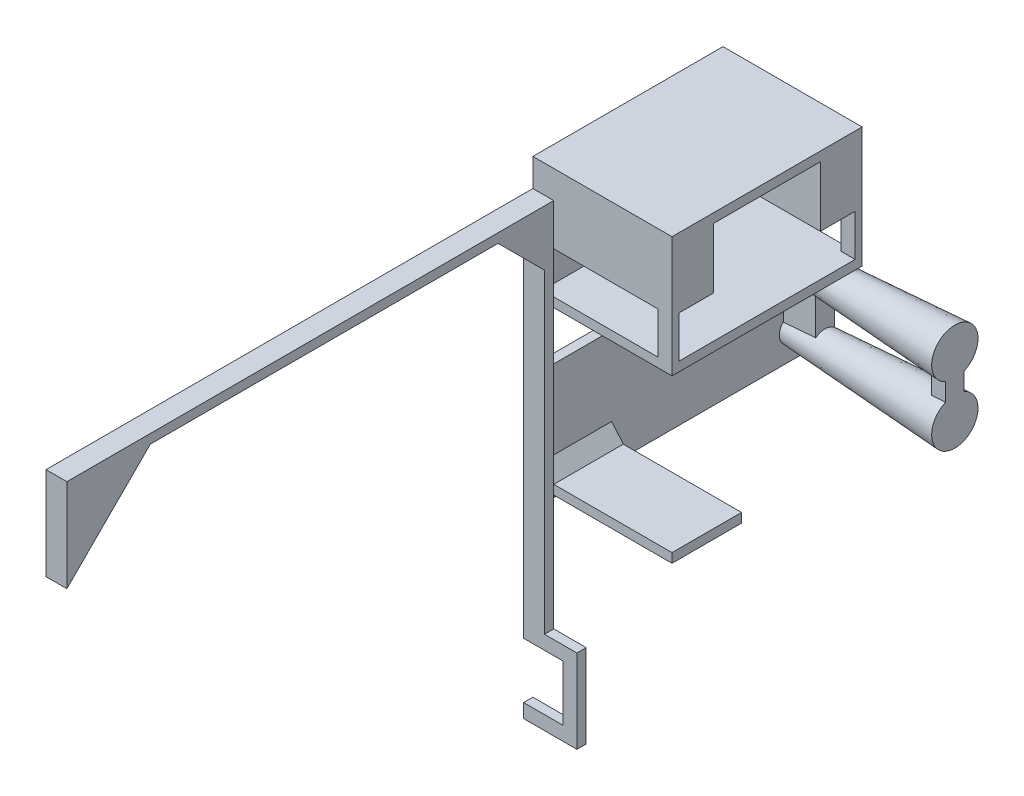
SolidWorks part; units mm, degrees
ref_plane "Front Plane" through (0, 0, 0) normal (0, 0, 1) x (1, 0, 0)
ref_plane "Top Plane" through (0, 0, 0) normal (0, 1, 0) x (1, 0, 0)
ref_plane "Right Plane" through (0, 0, 0) normal (1, 0, 0) x (0, 0, -1)
sketch "Sketch6" plane through (0, 0, 0) normal (1, 0, 0) x (0, 0, -1)
  line L1 (0, 0) -> (105, 0)
  line L2 (0, 0) -> (0, -83)
  line L3 (0, -83) -> (105, -83)
  line L4 (105, 0) -> (105, -83)
  dimension "D1" = 105
  dimension "D2" = 83
extrude "Boss-Extrude3" add sketch "Sketch6" along normal blind 4.5
sketch "Sketch9" plane through (0, -83, 0) normal (0, -1, 0) x (1, 0, 0)
  line L0 (4.5, 0) -> (4.5, -105) construction
  line L1 (0, 0) -> (0, -105) construction
  line L2 (4.5, -2) -> (1.5, -2)
  line L3 (4.5, -2) -> (4.5, -103)
  line L4 (4.5, -103) -> (1.5, -103)
  line L5 (1.5, -2) -> (1.5, -103)
  line L6 (4.5, 0) -> (0, 0) construction
  line L7 (4.5, -105) -> (0, -105) construction
  dimension "D1" = 1.5
  dimension "D2" = 2
  dimension "D3" = 2
extrude "Cut-Extrude6" cut sketch "Sketch9" against normal blind 81
sketch "Sketch10" plane through (0, 0, -2) normal (0, 0, -1) x (-1, 0, 0)
  line L1 (-4.5, -2) -> (-3.5, -2)
  line L2 (-4.5, -2) -> (-4.5, -10)
  line L3 (-4.5, -10) -> (-3.5, -10)
  line L4 (-3.5, -2) -> (-3.5, -10)
  dimension "D1" = 1
  dimension "D2" = 8
extrude "Boss-Extrude4" add sketch "Sketch10" along normal blind 8
sketch "Sketch11" plane through (0, 0, -103) normal (0, 0, 1) x (1, 0, 0)
  line L1 (4.5, -2) -> (3.2738, -2)
  line L2 (4.5, -2) -> (4.5, -7)
  line L3 (4.5, -7) -> (3.2738, -7)
  line L4 (3.2738, -2) -> (3.2738, -7)
  dimension "D1" = 5
extrude "Boss-Extrude5" add sketch "Sketch11" along normal blind 5
sketch "Sketch18" plane through (4.5, 0, 0) normal (1, 0, 0) x (0, 0, -1)
  line L0 (103, -12) -> (93, -2)
  line L1 (103, -7) -> (103, -83) construction
  line L2 (98, -2) -> (10, -2) construction
  line L3 (103, -12) -> (103, -2)
  line L4 (103, -2) -> (93, -2)
  line L5 (18, -2) -> (2, -2)
  line L6 (2, -2) -> (2, -18)
  line L7 (2, -10) -> (2, -83) construction
  line L8 (2, -18) -> (18, -2)
  dimension "D1" = 0
  dimension "D2" = 10
  dimension "D3" = 0
  dimension "D4" = 16
  dimension "D5" = 22.6274
extrude "Boss-Extrude12" add sketch "Sketch18" against normal up to vertex (1.2262 mm away) up to point (3.2738, -7, -98)
sketch "Sketch27" plane through (0, 0, 0) normal (-1, 0, 0) x (0, 0, 1)
  line L0 (-105, -83) -> (-105, 0) construction
  line L1 (-105, -55) -> (-120, -55)
  line L2 (-105, -55) -> (-105, -53)
  line L3 (-105, -53) -> (-120, -53)
  line L4 (-120, -55) -> (-120, -53)
  line L5 (-125.5, -18) -> (-125.5, 21.7068) construction
  line L6 (-105, -20) -> (-146, -20)
  line L7 (-105, -20) -> (-105, -18)
  line L8 (-105, -18) -> (-146, -18)
  line L9 (-146, -20) -> (-146, -18)
  line L10 (-105, -9) -> (-114, -9)
  line L11 (-105, -9) -> (-105, 6)
  line L12 (-105, 6) -> (-114, 6)
  line L13 (-114, -9) -> (-114, 6)
  line L14 (-146, 6) -> (-137, 6)
  line L15 (-137, -9) -> (-137, 6)
  line L16 (-146, -9) -> (-137, -9)
  line L17 (-146, -9) -> (-146, 6)
  dimension "D1" = 15
  dimension "D2" = 28
  dimension "D3" = 63
  dimension "D4" = 41
  dimension "D5" = 2
  dimension "D6" = 2
  dimension "D7" = 9
  dimension "D8" = 15
  dimension "D9" = 9
extrude "Boss-Extrude20" add sketch "Sketch27" against normal blind 30
sketch "Sketch28" plane through (30, 0, 0) normal (1, 0, 0) x (0, 0, -1)
  line L0 (146, -9) -> (137, -9) construction
  line L1 (146, -20) -> (144.5, -20)
  line L2 (146, -20) -> (146, -9)
  line L3 (146, -9) -> (144.5, -9)
  line L4 (144.5, -20) -> (144.5, -9)
  line L5 (125.5, -18) -> (125.5, -4.7212) construction
  line L6 (105, -18) -> (146, -18) construction
  line L7 (105, -9) -> (106.5, -9)
  line L8 (106.5, -20) -> (106.5, -9)
  line L9 (105, -20) -> (106.5, -20)
  line L10 (105, -20) -> (105, -9)
  dimension "D1" = 1.5
extrude "Boss-Extrude21" add sketch "Sketch28" against normal blind 3
sketch "Sketch29" plane through (30, 0, 0) normal (1, 0, 0) x (0, 0, -1)
  line L0 (105, -20) -> (105, 6) construction
  line L1 (146, 6) -> (105, 6)
  line L2 (146, 6) -> (146, 4)
  line L3 (146, 4) -> (105, 4)
  line L4 (105, 6) -> (105, 4)
  dimension "D1" = 2
extrude "Boss-Extrude22" add sketch "Sketch29" against normal up to vertex (30 mm away) up to point (0, 6, -105)
sketch "Sketch30" plane through (0, 0, -105) normal (0, 0, -1) x (-1, 0, 0)
  line L0 (0, -83) -> (0, -55) construction
  line L1 (0, -58) -> (-2, -58)
  line L2 (0, -58) -> (0, -33)
  line L3 (0, -33) -> (-2, -33)
  line L4 (-2, -58) -> (-2, -33)
  dimension "D1" = 2
  dimension "D2" = 25
  dimension "D3" = 25
extrude "Boss-Extrude23" add sketch "Sketch30" along normal blind 60
sketch "Sketch31" plane through (2, 0, 0) normal (1, 0, 0) x (0, 0, -1)
  line L0 (165, -58) -> (105, -58) construction
  line L1 (165, -33) -> (165, -58) construction
  line L2 (165, -45.5) -> (129.1416, -45.5) construction
  circle A0 centre (159, -52) radius 5
  circle A1 centre (159, -39) radius 5
  dimension "D1" = 10
  dimension "D2" = 6
  dimension "D3" = 6
extrude "Boss-Extrude24" add sketch "Sketch31" along normal blind 35
draft "Draft1" type of draft neutral plane draft angle 3.5 faces to draft 1 face at (37, -52, -164) neutral plane through (37, -52, -159) neutral plane normal (1, 0, 0) reverse direction yes parameters "D1"=3.5
draft "Draft3" type of draft neutral plane draft angle 3.5 faces to draft 1 face at (37, -39, -154) neutral plane through (37, -39, -159) neutral plane normal (1, 0, 0) reverse direction yes parameters "D1"=3.5
sketch "Sketch32" plane through (2, 0, 0) normal (1, 0, 0) x (0, 0, -1)
  line L1 (161, -53) -> (157, -53)
  line L2 (161, -53) -> (161, -38)
  line L3 (161, -38) -> (157, -38)
  line L4 (157, -53) -> (157, -38)
  circle A0 centre (159, -52) radius 2.8593 construction
  circle A1 centre (159, -39) radius 2.8593 construction
  dimension "D1" = 2
  dimension "D2" = 2
  dimension "D3" = 1
  dimension "D4" = 1
  dimension "D5" = 2
extrude "Boss-Extrude25" add sketch "Sketch32" along normal blind 7
sketch "Sketch33" plane through (37, 0, 0) normal (1, 0, 0) x (0, 0, -1)
  line L1 (157, -39) -> (161, -39)
  line L2 (157, -39) -> (157, -52)
  line L3 (157, -52) -> (161, -52)
  line L4 (161, -39) -> (161, -52)
  circle A0 centre (159, -39) radius 5 construction
  circle A1 centre (159, -52) radius 5 construction
  point P6 (159, -39)
  dimension "D1" = 0
  dimension "D2" = 4
  dimension "D3" = 0
  dimension "D4" = 0
extrude "Boss-Extrude26" add sketch "Sketch33" against normal blind 3
sketch "Sketch34" plane through (4.5, 0, 0) normal (1, 0, 0) x (0, 0, -1)
  line L0 (105, -83) -> (105, -55) construction
  line L1 (103, -83) -> (105, -83)
  line L2 (103, -83) -> (103, -80)
  line L3 (103, -80) -> (105, -80)
  line L4 (105, -83) -> (105, -80)
  dimension "D1" = 3
extrude "Boss-Extrude27" add sketch "Sketch34" along normal blind 4
sketch "Sketch35" plane through (8.5, 0, 0) normal (1, 0, 0) x (0, 0, -1)
  line L0 (105, -83) -> (105, -80) construction
  line L1 (103, -80) -> (105, -80)
  line L2 (103, -80) -> (103, -95)
  line L3 (103, -95) -> (105, -95)
  line L4 (105, -80) -> (105, -95)
  dimension "D1" = 0
  dimension "D2" = 15
extrude "Boss-Extrude28" add sketch "Sketch35" along normal blind 3
sketch "Sketch36" plane through (0, -95, 0) normal (0, -1, 0) x (-1, 0, 0)
  line L0 (0, 0) -> (0, 105) construction
  line L1 (-11.5, 103) -> (0, 103)
  line L2 (-11.5, 103) -> (-11.5, 105)
  line L3 (-11.5, 105) -> (0, 105)
  line L4 (0, 103) -> (0, 105)
  dimension "D1" = 0
extrude "Boss-Extrude29" add sketch "Sketch36" along normal blind 3
sketch "Sketch38" plane through (4.5, 0, 0) normal (1, 0, 0) x (0, 0, -1)
  line L0 (18, -2) -> (0, -20)
  line L1 (0, 0) -> (0, -83) construction
  line L2 (0, -20) -> (0, -83)
  line L3 (0, -83) -> (103, -83)
  line L4 (103, -83) -> (103, -12)
  line L5 (103, -12) -> (93, -2)
  line L6 (93, -2) -> (18, -2)
extrude "Cut-Extrude8" cut sketch "Sketch38" against normal blind 13
sketch "Sketch39" plane through (0, 0, 0) normal (-1, 0, 0) x (0, 0, 1)
  line L1 (-146, 6) -> (-105, 6)
  line L2 (-146, 6) -> (-146, -20)
  line L3 (-146, -20) -> (-105, -20)
  line L4 (-105, 6) -> (-105, -20)
extrude "Boss-Extrude30" add sketch "Sketch39" against normal blind 2
sketch "Sketch40" plane through (2, 0, 0) normal (1, 0, 0) x (0, 0, -1)
  line L1 (114, 4) -> (137, 4) construction
  line L2 (114, -9) -> (114, 4) construction
  circle A0 centre (125.5, -6.5) radius 5
  point P4 (125.5, 4)
  point P7 (114, -2.5)
  dimension "D1" = 0
  dimension "D2" = 4
  dimension "D3" = 10
extrude "Cut-Extrude9" cut sketch "Sketch40" against normal blind 2
sketch "Sketch41" plane through (0, 0, -120) normal (0, 0, -1) x (-1, 0, 0)
  line L0 (-2, -54) -> (-7.9406, -54) construction
  line L1 (-2, -55) -> (-2, -53) construction
  line L2 (-2, -55) -> (-2, -58)
  line L3 (-2, -58) -> (-4.5, -55)
  line L4 (-30, -55) -> (-2, -55) construction
  line L5 (-4.5, -55) -> (-2, -55)
  line L7 (-2, -50) -> (-4.5, -53)
  line L8 (-2, -53) -> (-2, -50)
  line L9 (-4.5, -53) -> (-2, -53)
  dimension "D1" = 0
  dimension "D2" = 0
extrude "Boss-Extrude31" add sketch "Sketch41" along direction (0, 0, 1) on the side against the normal up to surface (15 mm away) up to face at (2.1667, -35.3333, -105)
